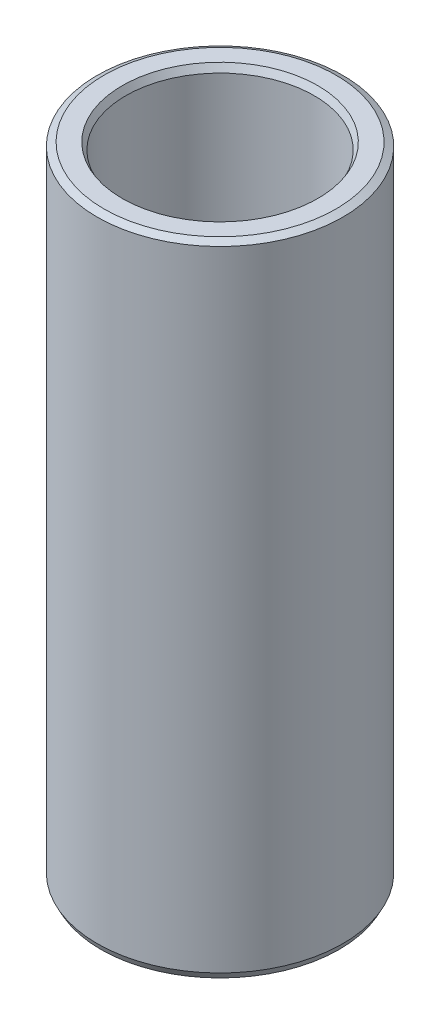
SolidWorks part; units mm, degrees
ref_plane "Front Plane" through (0, 0, 0) normal (0, 0, 1) x (1, 0, 0)
ref_plane "Top Plane" through (0, 0, 0) normal (0, 1, 0) x (1, 0, 0)
ref_plane "Right Plane" through (0, 0, 0) normal (1, 0, 0) x (0, 0, -1)
sketch "Sketch1" plane through (0, 0, 0) normal (0, 1, 0) x (1, 0, 0)
  circle A0 centre (0, 0) radius 45
  dimension "SLEEVE_OD" = 90
extrude "Boss-Extrude1" add sketch "Sketch1" along normal blind 234.3215
sketch "Sketch2" plane through (0, 0, 0) normal (0, 1, 0) x (1, 0, 0)
  circle A0 centre (0, 0) radius 34.5071
  dimension "BORE_D" = 69.0141
extrude "Cut-Extrude1" cut sketch "Sketch2" along normal through all
chamfer "Chamfer1" distance 1.324 angle 62.205 4 edges at (0, 234.3215, 34.5071) (0, 0, 34.5071) (0, 0, 45) (0, 234.3215, 45) first distance on face at (0, 234.3215, 34.5071) first distance on face at (0, 0, 34.5071) first distance on face at (0, 234.3215, 45)
